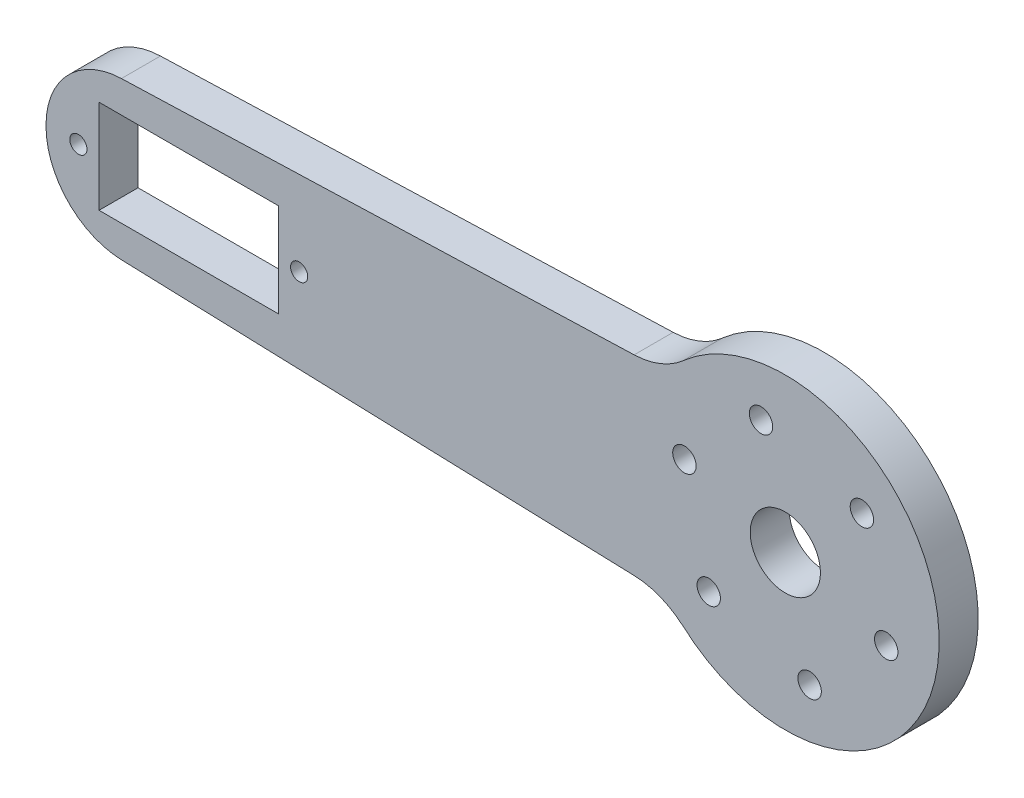
SolidWorks part; units mm, degrees
ref_plane "Front Plane" through (0, 0, 0) normal (0, 0, 1) x (1, 0, 0)
ref_plane "Top Plane" through (0, 0, 0) normal (0, 1, 0) x (1, 0, 0)
ref_plane "Right Plane" through (0, 0, 0) normal (1, 0, 0) x (0, 0, -1)
sketch "Sketch1" plane through (0, 0, 0) normal (0, 0, 1) x (1, 0, 0)
  line L0 (-49.0196, 0) -> (-45.7516, 0) construction
  line L5 (-49.0196, 9.8039) -> (49.0196, -9.8039) construction
  line L6 (-49.0196, -9.8039) -> (49.0196, 9.8039) construction
  line L7 (-45.7516, 0) -> (-19.6078, 0) construction
  line L8 (49.0196, 0) -> (45.7516, 0) construction
  line L9 (-44.1797, 6) -> (-21.1797, 6)
  line L10 (-44.1797, 6) -> (-44.1797, -6)
  line L11 (-44.1797, -6) -> (-21.1797, -6)
  line L12 (-21.1797, 6) -> (-21.1797, -6)
  line L13 (-44.1797, 6) -> (-21.1797, -6) construction
  line L14 (-44.1797, -6) -> (-21.1797, 6) construction
  line L15 (45.7516, 0) -> (41.8301, 0) construction
  line L16 (49.0196, 13.0719) -> (49.0196, -13.0719)
  line L17 (49.0196, 13.0719) -> (-49.0196, 9.8039)
  line L18 (49.0196, -13.0719) -> (-49.0196, -9.8039)
  line L19 (-49.0196, 9.8039) -> (-50.9804, 9.8039)
  line L20 (-50.9804, 9.8039) -> (-50.9804, -9.8039)
  line L21 (-50.9804, -9.8039) -> (-49.0196, -9.8039)
  circle A0 centre (43.7908, 0) radius 1.9608
  point P0 (0, 0)
  point P9 (-32.6797, 0)
  point P22 (49.0196, 0)
  dimension "D1" = 100
  dimension "D2" = 23
  dimension "D3" = 12
extrude "Boss-Extrude1" add sketch "Sketch1" along normal blind 5
fillet "Fillet2" radius 20 2 edges at (49.0196, -13.0719, 2.5) (49.0196, 13.0719, 2.5)
sketch "Sketch3" plane through (0, 0, 5) normal (0, 0, 1) x (1, 0, 0)
  circle A0 centre (43.7908, 0) radius 19.7224
  circle A1 centre (43.7908, 0) radius 3
extrude "Boss-Extrude2" add sketch "Sketch3" against normal up to surface (5 mm away) up to face at (-13.1283, 0, 0)
fillet "Fillet3" radius 10 4 edges at (-50.9804, 9.8039, 2.5) (-50.9804, -9.8039, 2.5) (28.4427, -12.3858, 2.5) (28.4427, 12.3858, 2.5)
sketch "Sketch6" plane through (0, 0, 5) normal (0, 0, 1) x (1, 0, 0)
  circle A0 centre (43.7908, 0) radius 4.5
extrude "Cut-Extrude3" cut sketch "Sketch6" against normal blind 6
sketch "Sketch7" plane through (0, 0, 5) normal (0, 0, 1) x (1, 0, 0)
  circle A0 centre (53.6083, 9.2665) radius 1.5
  circle A1 centre (43.7908, 0) radius 4.5
  circle A2 centre (56.7246, -3.8689) radius 1.5
  circle A3 centre (46.9072, -13.1354) radius 1.5
  circle A4 centre (33.9734, -9.2665) radius 1.5
  circle A5 centre (30.8571, 3.8689) radius 1.5
  circle A6 centre (40.6745, 13.1354) radius 1.5
  point P17 (43.7908, 0)
  dimension "D1" = 3
  dimension "D4" = 9
  dimension "D2" = 13.5
  dimension "D3" = 6
extrude "Cut-Extrude4" cut sketch "Sketch7" against normal blind 10
sketch "Sketch9" plane through (0, 0, 5) normal (0, 0, 1) x (1, 0, 0)
  line L0 (-44.1797, 6) -> (-44.1797, -6) construction
  circle A0 centre (-46.8297, 0) radius 1.1
  circle A1 centre (-18.5297, 0) radius 1.1
  point P4 (-44.1797, 0)
  dimension "D1" = 2.2
  dimension "D2" = 2.65
extrude "Cut-Extrude6" cut sketch "Sketch9" against normal blind 10
